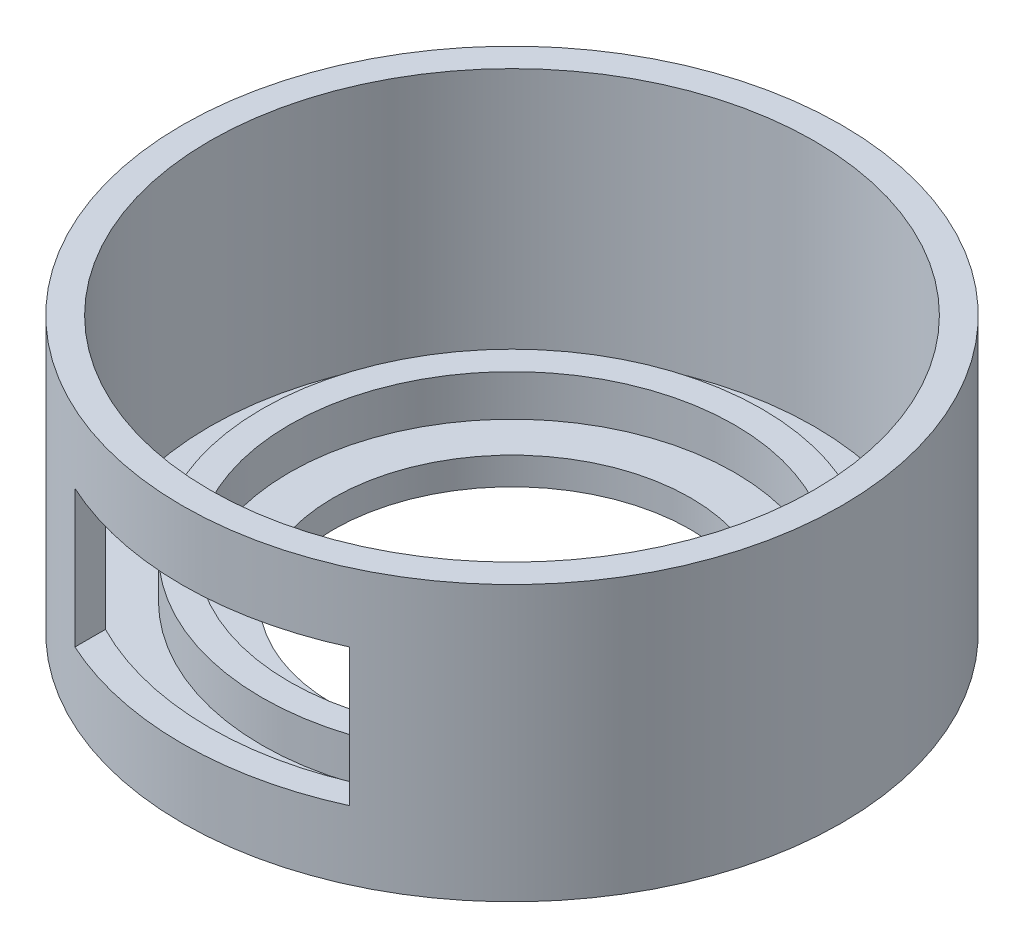
SolidWorks part; units mm, degrees
other "Marca1"
sketch "Croquis9" plane through (75, 36.0719, 2) normal (0.7684, 0.4514, 0.4536) x (0.4736, 0.0756, -0.8775)
ref_plane "Alzado" through (0, 0, 0) normal (0, 0, 1) x (1, 0, 0)
ref_plane "Planta" through (0, 0, 0) normal (0, 1, 0) x (1, 0, 0)
ref_plane "Vista lateral" through (0, 0, 0) normal (1, 0, 0) x (0, 0, -1)
sketch "Croquis1" plane through (0, 0, 0) normal (0, 1, 0) x (1, 0, 0)
  circle A0 centre (8.8, 6.6) radius 6.5
  circle A1 centre (8.8, 6.6) radius 8.1
  circle A2 centre (8.8, 6.6) radius 9.1
  circle A3 centre (8.8, 6.6) radius 11
  circle A4 centre (8.8, 6.6) radius 12
  dimension "D3" = 13
  dimension "D4" = 16.2
  dimension "D2" = 22
  dimension "D1" = 1
  dimension "D5" = 1
extrude "Saliente-Extruir2" add sketch "Croquis1" along normal blind 1 contours A2 | A1 A0 | A2 A1 region at (0.9291, 0, -6.6) region at (-0.0426, 0, -6.6) region at (-1.8889, 0, -6.6)
extrude "Saliente-Extruir3" add sketch "Croquis1<6>" along normal blind 2.5 contours A2 A1 region at (-0.0426, 0, -6.6)
sketch "Croquis1<6>" plane through (0, 0, 0) normal (0, 1, 0) x (1, 0, 0) same geometry as "Croquis1"
extrude "Saliente-Extruir4" add sketch "Croquis1<8>" along normal blind 10 contours A4 A3 region at (-2.8606, 0, -6.6)
sketch "Croquis1<8>" plane through (0, 0, 0) normal (0, 1, 0) x (1, 0, 0) same geometry as "Croquis1"
sketch "Croquis10" plane through (0, 0, 0) normal (0, 0, 1) x (1, 0, 0)
  line L0 (8.8, 10) -> (8.8, 0)
  line L1 (20.8, 10) -> (-3.2, 10) construction
  line L2 (-3.2, 0) -> (20.8, 0) construction
  line L4 (3.8, 2.5) -> (13.8, 2.5)
  line L5 (3.8, 2.5) -> (3.8, 7.5)
  line L6 (3.8, 7.5) -> (13.8, 7.5)
  line L7 (13.8, 2.5) -> (13.8, 7.5)
  line L8 (3.8, 2.5) -> (13.8, 7.5) construction
  line L9 (3.8, 7.5) -> (13.8, 2.5) construction
  point P6 (8.8, 5)
  dimension "D1" = 5
  dimension "D2" = 10
extrude "Cortar-Extruir1" cut sketch "Croquis10" along normal blind 30 contours L4 L7 L6 L0 | L6 L5 L4 L0 region at (11.3, 5, 0) region at (6.3, 5, 0)
